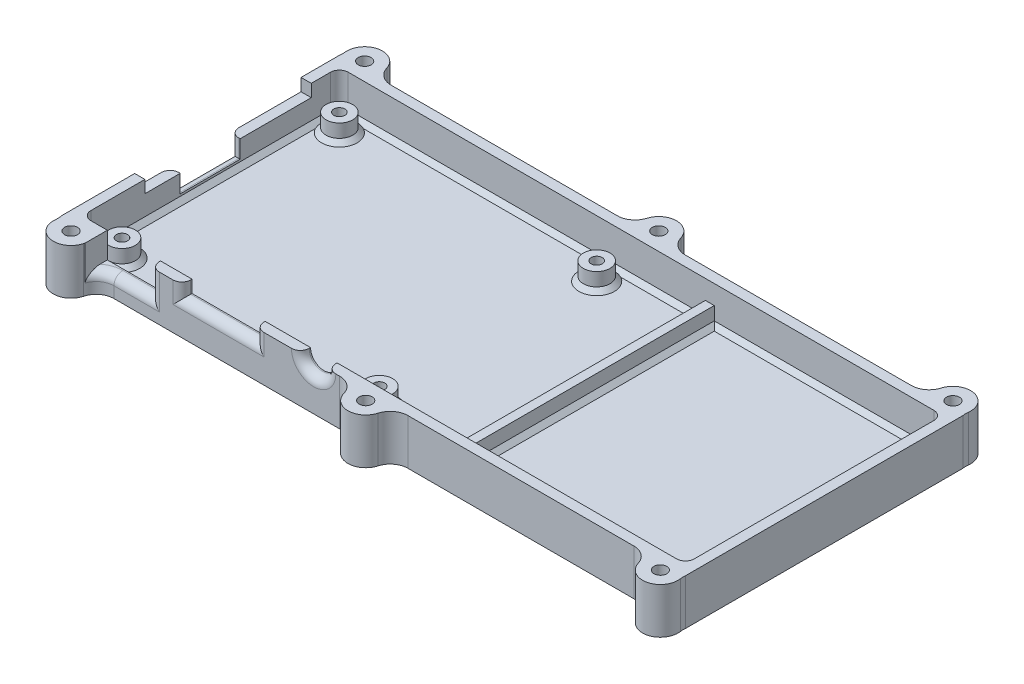
SolidWorks part; units mm, degrees
ref_plane "Front Plane" through (0, 0, 0) normal (0, 0, 1) x (1, 0, 0)
ref_plane "Top Plane" through (0, 0, 0) normal (0, 1, 0) x (1, 0, 0)
ref_plane "Right Plane" through (0, 0, 0) normal (1, 0, 0) x (0, 0, -1)
sketch "Sketch1" plane through (0, 0, 0) normal (0, 1, 0) x (1, 0, 0)
  line L0 (-71.5618, 3.106) -> (62.4382, 3.106) construction
  line L1 (-71.5618, 31.106) -> (62.4382, 31.106)
  line L2 (-71.5618, 31.106) -> (-71.5618, -24.894)
  line L3 (-71.5618, -24.894) -> (62.4382, -24.894)
  line L4 (62.4382, 31.106) -> (62.4382, -24.894)
  line L5 (-60.6618, -24.894) -> (-60.6618, -31.6828) construction
  line L6 (-68.0618, 27.606) -> (-10.0618, 27.606)
  line L7 (-68.0618, 27.606) -> (-68.0618, -21.394)
  line L8 (-68.0618, -21.394) -> (-10.0618, -21.394)
  line L9 (-10.0618, 27.606) -> (-10.0618, -21.394)
  line L10 (-39.5618, -24.894) -> (-39.5618, -31.6828) construction
  line L11 (-18.0618, -24.894) -> (-18.0618, -31.6828) construction
  line L12 (-65.4118, -26.5648) -> (-55.9118, -26.5648) construction
  line L13 (-48.0618, -26.5648) -> (-31.0618, -26.5648) construction
  line L14 (-22.0618, -26.5648) -> (-14.0618, -26.5648) construction
  line L15 (-72.5618, 9.606) -> (-72.5618, -3.394) construction
  line L16 (-71.5618, 3.106) -> (-72.5618, 3.106) construction
  dimension "D1" = 134
  dimension "D2" = 56
  dimension "D3" = 49
  dimension "D4" = 58
  dimension "D5" = 3.5
  dimension "D6" = 3.5
  dimension "D7" = 10.9
  dimension "D8" = 32
  dimension "D9" = 53.5
  dimension "D10" = 2
  dimension "D11" = 13
  dimension "D12" = 9.5
  dimension "D13" = 17
  dimension "D14" = 8
sketch "Sketch3" plane through (0, 0, 0) normal (0, 1, 0) x (1, 0, 0)
  line L4 (65.7382, 34.406) -> (-74.8618, 34.406)
  line L5 (-74.8618, 34.406) -> (-74.8618, -28.194)
  line L6 (-74.8618, -28.194) -> (65.7382, -28.194)
  line L7 (65.7382, -28.194) -> (65.7382, 34.406)
  line L8 (63.4382, 32.106) -> (-72.5618, 32.106)
  line L9 (63.4382, -25.894) -> (63.4382, 32.106)
  line L10 (-72.5618, -25.894) -> (63.4382, -25.894)
  line L11 (-72.5618, 32.106) -> (-72.5618, -25.894)
  line L12 (63.4382, 32.106) -> (-72.5618, 32.106)
  line L13 (63.4382, -25.894) -> (63.4382, 32.106)
  line L14 (-72.5618, -25.894) -> (63.4382, -25.894)
  line L15 (-72.5618, 32.106) -> (-72.5618, -25.894)
  line L16 (-4.5618, 3.106) -> (-4.5618, 34.406) construction
  line L17 (-71.5618, 3.106) -> (62.4382, 3.106) construction
  line L20 (-74.8618, 3.106) -> (65.7382, 3.106) construction
  dimension "D1" = 1
  dimension "D2" = 2.3
extrude "Boss-Extrude1" add sketch "Sketch3" along normal blind 10.3
sketch "Sketch5" plane through (0, 0, 0) normal (0, 1, 0) x (1, 0, 0)
  line L1 (-72.5618, 32.106) -> (63.4382, 32.106)
  line L2 (-72.5618, 32.106) -> (-72.5618, -25.894)
  line L3 (-72.5618, -25.894) -> (63.4382, -25.894)
  line L4 (63.4382, 32.106) -> (63.4382, -25.894)
extrude "Boss-Extrude2" add sketch "Sketch5" along normal blind 2
sketch "Sketch6" plane through (0, 2, 0) normal (0, 1, 0) x (1, 0, 0)
  circle A0 centre (-68.0618, 27.606) radius 3
  circle A1 centre (-68.0618, -21.394) radius 3
  circle A2 centre (-10.0618, -21.394) radius 3
  circle A3 centre (-10.0618, 27.606) radius 3
extrude "Boss-Extrude3" add sketch "Sketch6" along normal blind 4
hole_wizard "Ø2.5 (2.5) Diameter Hole1" positions "Sketch8" profile "Sketch9" hole size "Ø2.5" standard "ANSI Metric"
sketch "Sketch8" plane through (0, 6, 0) normal (0, 1, 0) x (1, 0, 0)
  point P0 (-68.0618, 27.606)
  point P3 (-10.0618, 27.606)
  point P6 (-10.0618, -21.394)
  point P9 (-68.0618, -21.394)
sketch "Sketch9" plane through (-68.0618, 6, -27.606) normal (1, 0, 0) x (0, 0, 1)
  line L0 (0, 0) -> (0, 8.7511)
  line L1 (0, 8.7511) -> (1.25, 8)
  line L2 (1.25, 8) -> (1.25, 0)
  line L5 (1.25, 0) -> (0, 0)
  line L10 (0, 8.7511) -> (-1.25, 8) construction
  line L11 (0, -6.35) -> (0, 107.95) construction
  dimension "Hole Dia." = 2.5
  dimension "Hole Depth" = 8
  dimension "Drill Angle" = 118
sketch "Sketch10" plane through (0, 2, 0) normal (0, 1, 0) x (1, 0, 0)
  line L0 (63.4382, 32.106) -> (-72.5618, 32.106) construction
  line L1 (9.9382, 32.106) -> (11.9382, 32.106)
  line L2 (9.9382, 32.106) -> (9.9382, -25.894)
  line L3 (9.9382, -25.894) -> (11.9382, -25.894)
  line L4 (11.9382, 32.106) -> (11.9382, -25.894)
  line L5 (-72.5618, -25.894) -> (63.4382, -25.894) construction
  line L6 (-10.0618, 27.606) -> (-10.0618, -21.394) construction
  dimension "D1" = 2
  dimension "D2" = 20
extrude "Boss-Extrude4" add sketch "Sketch10" along normal blind 4
sketch "Sketch11" plane through (0, 0, 28.194) normal (0, 0, 1) x (1, 0, 0)
  line L0 (-74.8618, 10.3) -> (-74.8618, 0) construction
  line L1 (-66.8618, 10.3) -> (-54.8618, 10.3)
  line L2 (-66.8618, 10.3) -> (-66.8618, 4.5)
  line L3 (-66.8618, 4.5) -> (-54.8618, 4.5)
  line L4 (-54.8618, 10.3) -> (-54.8618, 4.5)
  line L5 (-74.8618, 0) -> (65.7382, 0) construction
  line L6 (-60.8618, 10.3) -> (-60.6618, 0) construction
  line L7 (-65.4118, 0) -> (-55.9118, 0) construction
  line L9 (-47.778, 10.3) -> (-31.278, 10.3)
  line L10 (-47.778, 10.3) -> (-47.778, 7.5)
  line L11 (-47.778, 7.5) -> (-31.278, 7.5)
  line L12 (-31.278, 10.3) -> (-31.278, 7.5)
  line L13 (-68.0618, 0) -> (-10.0618, 0) construction
  line L14 (-39.5618, 0) -> (-39.528, 10.3) construction
  line L15 (-48.0618, 0) -> (-31.0618, 0) construction
  line L16 (-18.0618, 0) -> (-18.0618, 10.3) construction
  line L17 (-22.0618, 0) -> (-14.0618, 0) construction
  line L18 (-74.8618, 10.3) -> (65.7382, 10.3) construction
  circle A0 centre (-18.0618, 10.3) radius 3
  dimension "D5" = 6
  dimension "D1" = 4.5
  dimension "D2" = 12
  dimension "D3" = 7.5
  dimension "D4" = 16.5
  dimension "D6" = 8
extrude "Cut-Extrude1" cut sketch "Sketch11" against normal up to next
sketch "Sketch12" plane through (-74.8618, 0, 0) normal (-1, 0, 0) x (0, 0, 1)
  line L0 (-3.106, 0) -> (-3.106, 10.3) construction
  line L1 (-27.606, 0) -> (21.394, 0) construction
  line L2 (-34.406, 10.3) -> (28.194, 10.3) construction
  line L4 (-9.7329, 10.3) -> (3.7671, 10.3)
  line L5 (-9.7329, 10.3) -> (-9.7329, 3.5)
  line L6 (-9.7329, 3.5) -> (3.7671, 3.5)
  line L7 (3.7671, 10.3) -> (3.7671, 3.5)
  line L8 (-25.7667, 10.3) -> (11.7333, 10.3)
  line L9 (-25.7667, 10.3) -> (-25.7667, 7.5)
  line L10 (-25.7667, 7.5) -> (11.7333, 7.5)
  line L11 (11.7333, 10.3) -> (11.7333, 7.5)
  line L13 (-25.7667, 7.5) -> (-25.7667, 10.3)
  dimension "D1" = 13.5
  dimension "D2" = 3.5
  dimension "D3" = 7.5
  dimension "D4" = 37.5
extrude "Cut-Extrude2" cut sketch "Sketch12" against normal up to next contours L10 L11 L8 L9 | L7 L6 L5 L4
sketch "Sketch13" plane through (0, 0, 0) normal (0, 1, 0) x (1, 0, 0)
  line L0 (-74.8618, 34.406) -> (-74.8618, 42.3177) construction
  line L1 (65.7382, 34.406) -> (65.7382, 40.5826) construction
  line L2 (-74.8618, 2.9829) -> (65.7382, 3.106) construction
  line L3 (-74.8618, 9.7329) -> (-74.8618, -3.7671) construction
  line L4 (9.9382, 32.106) -> (-72.5618, 32.106) construction
  line L5 (65.7382, -28.194) -> (65.7382, 34.406) construction
  circle A0 centre (-70.8618, 36.106) radius 4
  circle A1 centre (-4.5618, 36.106) radius 4
  circle A2 centre (61.7382, 36.106) radius 4
  circle A3 centre (61.796, -29.901) radius 4
  circle A4 centre (-4.5039, -30.017) radius 4
  circle A5 centre (-70.8038, -30.1331) radius 4
  dimension "D1" = 4
  dimension "D3" = 4
  dimension "D2" = 4
extrude "Boss-Extrude5" add sketch "Sketch13" along normal up to vertex (10.3 mm away) up to point (-15.0618, 10.3, 28.194)
fillet "Fillet2" radius 4 1 edges at (-74.4825, 5.15, -34.406)
fillet "Fillet3" radius 4 8 edges at (58.1785, 5.15, 28.194) (-67.3052, 5.15, 28.194) (-0.9435, 5.15, 28.194) (-8.0643, 5.15, 28.194) (58.1175, 5.15, -34.406) (-0.941, 5.15, -34.406) (-8.1825, 5.15, -34.406) (-67.241, 5.15, -34.406)
fillet "Fillet4" radius 4 3 edges at (-74.3023, 5.15, 28.194) (65.4135, 5.15, 28.194) (65.359, 5.15, -34.406)
hole_wizard "Ø2.9 (2.9) Diameter Hole1" positions "Sketch15" profile "Sketch16" hole size "Ø2.9" standard "ANSI Metric" end condition up to next
sketch "Sketch15" plane through (0, 10.3, 0) normal (0, 1, 0) x (1, 0, 0)
  point P0 (-70.8618, 36.106)
  point P3 (-4.5618, 36.106)
  point P6 (61.7382, 36.106)
  point P9 (61.796, -29.901)
  point P12 (-4.5039, -30.017)
  point P15 (-70.8038, -30.1331)
sketch "Sketch16" plane through (-70.8618, 10.3, -36.106) normal (1, 0, 0) x (0, 0, 1)
  line L0 (0, 0) -> (0, 10.3)
  line L1 (0, 10.3) -> (1.45, 10.3)
  line L2 (1.45, 10.3) -> (1.45, 0)
  line L5 (1.45, 0) -> (0, 0)
  line L11 (0, -6.35) -> (0, 107.95) construction
  dimension "Thru Hole Dia." = 2.9
  dimension "Thru Hole Depth" = 10.3
fillet "Fillet6" radius 2 1 edges at (63.4382, 6.15, -32.106)
fillet "Fillet7" radius 2 1 edges at (63.4382, 6.15, 25.894)
fillet "Fillet8" radius 2 2 edges at (-72.5618, 6.15, 25.894) (-72.5618, 6.15, -32.106)
chamfer "Chamfer1" distance 1 angle 45 4 edges at (-68.0618, 2, 24.394) (-10.0618, 2, 24.394) (-10.0618, 2, -24.606) (-68.0618, 2, -24.606)
chamfer "Chamfer2" distance 1 angle 45 12 edges at (11.9382, 2, -3.106) (36.6882, 2, 25.894) (36.6882, 2, -32.106) (62.8524, 2, 25.3082) (62.8524, 2, -31.5202) (63.4382, 2, -3.106) (-30.3118, 2, 25.894) (-71.976, 2, 25.3082) (-72.5618, 2, -3.106) (-71.976, 2, -31.5202) (9.9382, 2, -3.106) (-30.3118, 2, -32.106)
sketch "Sketch17" plane through (0, 0, 28.194) normal (0, 0, 1) x (1, 0, 0)
  line L0 (-53.9318, 4.5) -> (-63.0738, 4.5) construction
  line L1 (-66.9388, 10.3) -> (-54.9388, 10.3)
  line L2 (-66.9388, 10.3) -> (-66.9388, 4.5)
  line L3 (-66.9388, 4.5) -> (-54.9388, 4.5)
  line L4 (-54.9388, 10.3) -> (-54.9388, 4.5)
  dimension "D1" = 12
fillet "Fillet9" radius 2 10 edges at (-65.404, 4.5, 28.9428) (-74.8618, 5.5, -9.7329) (-74.8618, 3.5, -2.9829) (-74.8618, 5.5, 3.7671) (-18.0618, 7.3, 28.194) (-31.278, 8.9, 28.194) (-47.778, 8.9, 28.194) (-39.528, 7.5, 28.194) (-54.8618, 7.4, 28.194) (-58.9678, 4.5, 28.194)
